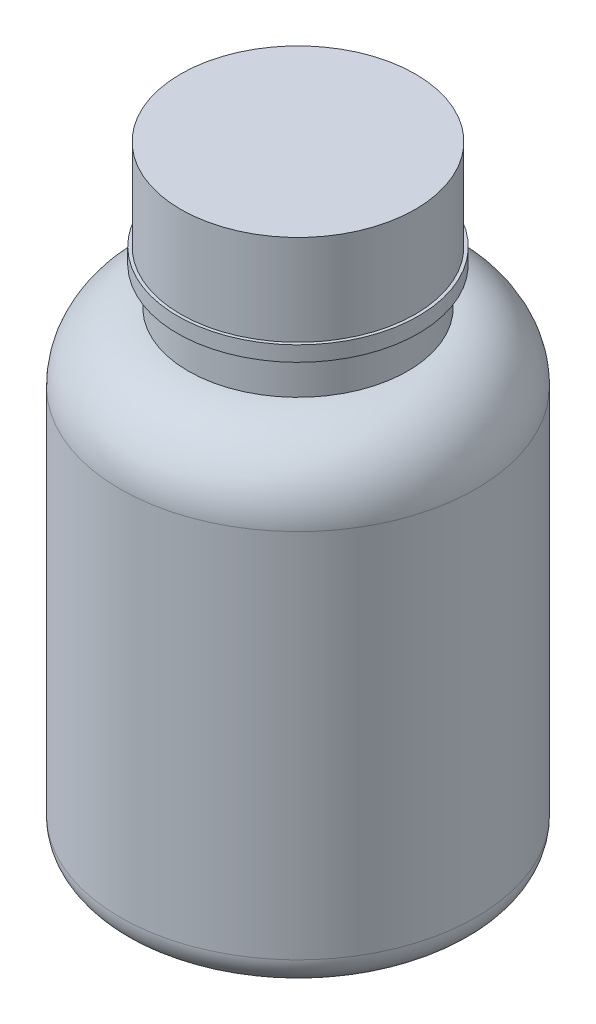
SolidWorks part; units mm, degrees
ref_plane "前视基准面" through (0, 0, 0) normal (0, 0, 1) x (1, 0, 0)
ref_plane "上视基准面" through (0, 0, 0) normal (0, 1, 0) x (1, 0, 0)
ref_plane "右视基准面" through (0, 0, 0) normal (1, 0, 0) x (0, 0, -1)
other "Configuration Table"
sketch "草图1" plane through (0, 0, 0) normal (0, 0, 1) x (1, 0, 0)
  line L0 (0, -4.7776) -> (0, 4.7776) construction
  line L1 (-15.909, 44) -> (-15.5, 44) construction
  line L2 (-19.5, -25) -> (19.5, -25)
  line L3 (-23.5, -21) -> (-23.5, 25)
  line L5 (23.5, -21) -> (23.5, 25)
  line L6 (-23.5, -25) -> (23.5, 25) construction
  line L7 (-23.5, 25) -> (23.5, -25) construction
  line L9 (-15.5, 44) -> (-15.5, 56)
  line L10 (-15.5, 56) -> (15.5, 56)
  line L11 (15.5, 44) -> (15.5, 56)
  line L12 (-15.5, 44) -> (15.5, 56) construction
  line L13 (-15.5, 56) -> (15.5, 44) construction
  line L16 (15.909, 44) -> (15.5, 44)
  line L17 (15.909, 44) -> (15.909, 42)
  line L18 (15.909, 42) -> (14.5, 42)
  line L19 (-15.909, 44) -> (-15.909, 42)
  line L20 (0, 0) -> (0, 73.7116) construction
  line L23 (-14.5, 42) -> (-14.5, 37)
  line L25 (14.5, 42) -> (14.5, 37)
  line L26 (23.5, 28) -> (23.5, 25)
  line L28 (-23.5, 28) -> (-23.5, 25)
  line L29 (-14.5, 42) -> (-15.909, 42)
  line L30 (-15.5, 44) -> (-15.909, 44)
  line L31 (15.5, 44) -> (15.909, 44) construction
  line L32 (0, 60.4044) -> (0, -40.3542)
  arc A2 (-19.5, -25) -> (-23.5, -21) centre (-19.5, -21) cw
  arc A3 (19.5, -25) -> (23.5, -21) centre (19.5, -21) ccw
  arc A4 (-14.5, 37) -> (-23.5, 28) centre (-14.5, 28) ccw
  arc A5 (14.5, 37) -> (23.5, 28) centre (14.5, 28) cw
  point P0 (0, 0)
  point P4 (0, 0)
  point P10 (0, 50)
  point P17 (0, 44)
  dimension "D8" = 4
  dimension "D11" = 9
  dimension "D1" = 47
  dimension "D2" = 50
  dimension "D3" = 81
  dimension "D4" = 31
  dimension "D5" = 12
  dimension "D6" = 2
  dimension "D7" = 0
revolve "旋转1" add sketch "草图1" angle 360 about L20 region at (10.9405, 12.5968, 0)
